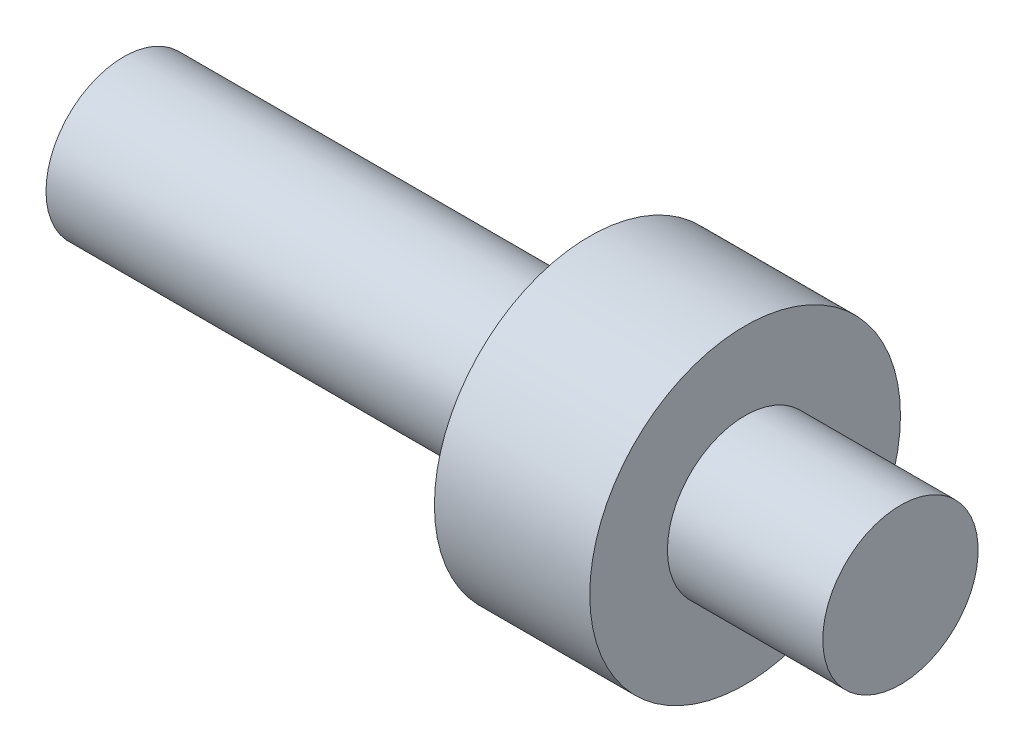
SolidWorks part; units mm, degrees
ref_plane "Front Plane" through (0, 0, 0) normal (0, 0, 1) x (1, 0, 0)
ref_plane "Top Plane" through (0, 0, 0) normal (0, 1, 0) x (1, 0, 0)
ref_plane "Right Plane" through (0, 0, 0) normal (1, 0, 0) x (0, 0, -1)
sketch "Sketch1" plane through (0, 0, 0) normal (0, 0, 1) x (1, 0, 0)
  line L0 (0, 0) -> (12.7, 0)
  line L1 (12.7, 0) -> (12.7, 3.175)
  line L2 (12.7, 3.175) -> (6.35, 3.175)
  line L3 (6.35, 3.175) -> (6.35, 6.35)
  line L4 (6.35, 6.35) -> (0, 6.35)
  line L5 (0, 6.35) -> (0, 3.175)
  line L6 (0, 3.175) -> (-19.05, 3.175)
  line L7 (-19.05, 3.175) -> (-19.05, 0)
  line L8 (-19.05, 0) -> (0, 0)
  line L9 (0, 0) -> (0, 3.175) construction
  dimension "D1" = 6.35
  dimension "pinRadius" = 3.175
  dimension "D2" = 19.05
  dimension "D3" = 6.35
  dimension "D4" = 6.35
revolve "Revolve1" add sketch "Sketch1" angle 360 about L8
